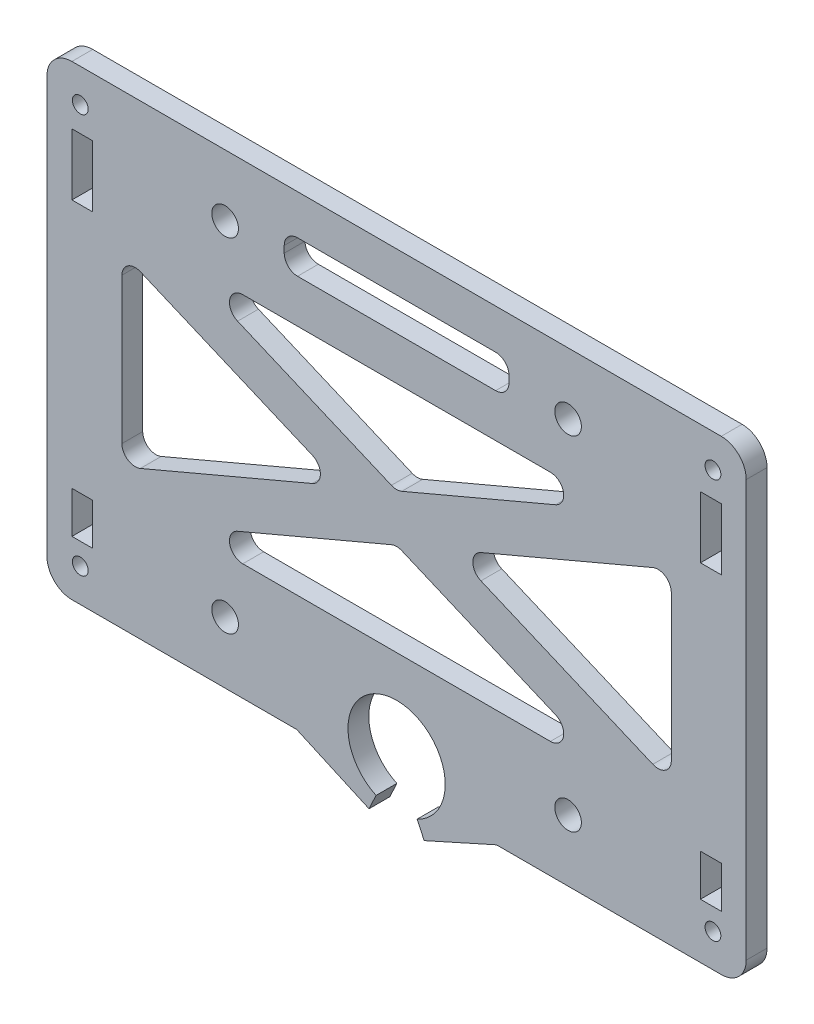
SolidWorks part; units mm, degrees
material "Delrin 2700 NC010, Low Viscosity Acetal Copolymer (SS)"
ref_plane "Front Plane" through (0, 0, 0) normal (0, 0, 1) x (1, 0, 0)
ref_plane "Top Plane" through (0, 0, 0) normal (0, 1, 0) x (1, 0, 0)
ref_plane "Right Plane" through (0, 0, 0) normal (1, 0, 0) x (0, 0, -1)
sketch "Sketch1" plane through (0, 0, 0) normal (0, 0, 1) x (1, 0, 0)
  line L0 (0, -1000) -> (0, 49000) construction
  line L1 (24.765, 17.78) -> (-24.765, 17.78)
  line L2 (26.67, 15.875) -> (26.67, -17.78)
  line L3 (26.67, -17.78) -> (-26.67, -17.78)
  line L4 (-26.67, 15.875) -> (-26.67, -17.78)
  line L5 (26.67, 17.78) -> (-26.67, -17.78) construction
  line L6 (26.67, -17.78) -> (-26.67, 17.78) construction
  line L7 (-1000, 0) -> (49000, 0) construction
  line L8 (-7.62, -17.78) -> (-2.104, -20.26)
  line L15 (-2.104, -20.26) -> (0, -15.748)
  line L16 (7.62, -17.78) -> (2.104, -20.26)
  line L17 (2.104, -20.26) -> (0, -15.748)
  line L18 (0, 0) -> (-24.2469, 20.3456) construction
  circle A0 centre (0, -15.748) radius 3.7084
  circle A1 centre (-24.13, 15.24) radius 0.6032
  circle A2 centre (-13.08, -13.08) radius 1.016
  circle A3 centre (24.13, 15.24) radius 0.6033
  circle A4 centre (-13.08, 13.08) radius 1.016
  circle A5 centre (13.08, 13.08) radius 1.016
  circle A6 centre (13.08, -13.08) radius 1.016
  arc A7 (24.765, -17.78) -> (26.67, -15.875) centre (24.765, -15.875) ccw
  arc A8 (-24.765, -17.78) -> (-26.67, -15.875) centre (-24.765, -15.875) cw
  arc A9 (-24.765, 17.78) -> (-26.67, 15.875) centre (-24.765, 15.875) ccw
  arc A10 (24.765, 17.78) -> (26.67, 15.875) centre (24.765, 15.875) cw
  circle A11 centre (24.13, -15.24) radius 0.6033
  circle A12 centre (-24.13, -15.24) radius 0.6032
  circle A13 centre (0, -15.748) radius 4.9784
  point P0 (0, 0)
  point P9 (0, 0)
  point P11 (0, -7.366)
  point P53 (-13.97, 0)
  dimension "D6" = 7.4168
  dimension "D7" = 1.2065
  dimension "D9" = 2.032
  dimension "D14" = 1.905
  dimension "D15" = 1.905
  dimension "D30" = 2.54
  dimension "D1" = 35.56
  dimension "D4" = 53.34
  dimension "D5" = 15.748
  dimension "D8" = 2.54
  dimension "D10" = 13.08
  dimension "D11" = 13.08
  dimension "D19" = 40
  dimension "D20" = 8.382
  dimension "D21" = 4
  dimension "D23" = 13.97
  dimension "D27" = 7.62
  dimension "D28" = 25
  dimension "D26" = 1.27
extrude "Boss-Extrude1" add sketch "Sketch1" along normal blind 1.5875 contours A10 L1 A9 L4 L3 A0 L2 A6 A5 A4 A1 A2 A3 | L3 A13 L15 A0 | A13 L3 L8 | L3 A13 A0 | L17 A13 L3 A0 | A13 L16 L3 region at (0, 0.4732, 0) region at (5.0756, -18.4873, 0) region at (-5.0756, -18.4873, 0) region at (2.9865, -18.87, 0) region at (3.8235, -17.6582, 0) region at (-2.9865, -18.87, 0)
ref_axis "Axis1" through (0, 0, 0) along (0, 0, 1)
sketch "Sketch2" plane through (0, 0, 1.5875) normal (0, 0, 1) x (1, 0, 0)
  line L0 (0, -1000) -> (0, 49000) construction
  line L1 (-1000, 0) -> (49000, 0) construction
  line L2 (21.0732, -7.1467) -> (-16.7276, 8.89)
  line L3 (20.955, 8.89) -> (-20.955, 8.89)
  line L4 (20.955, 8.89) -> (20.955, -8.89)
  line L5 (20.955, -8.89) -> (-20.955, -8.89)
  line L6 (-20.955, 8.89) -> (-20.955, -8.89)
  line L7 (20.955, 8.89) -> (-20.955, -8.89) construction
  line L8 (20.955, -8.89) -> (-20.955, 8.89) construction
  line L9 (16.7276, 8.89) -> (-20.955, -7.0966)
  line L10 (16.7276, -8.89) -> (-20.955, 7.0966)
  line L11 (20.955, 7.0966) -> (-16.7276, -8.89)
  line L12 (21.5998, 7.3701) -> (-20.3102, -10.4099) construction
  line L13 (20.3102, 10.4099) -> (-21.5998, -7.3701) construction
  line L14 (20.3102, -10.4099) -> (-21.5998, 7.3701) construction
  line L15 (21.5998, -7.3701) -> (-20.3102, 10.4099) construction
  line L16 (24.765, 17.78) -> (-24.765, 17.78) construction
  line L17 (8.5725, 14.732) -> (-8.5725, 14.732)
  line L18 (8.5725, 14.732) -> (8.5725, 12.192)
  line L19 (8.5725, 12.192) -> (-8.5725, 12.192)
  line L20 (-8.5725, 14.732) -> (-8.5725, 12.192)
  line L21 (8.5725, 14.732) -> (-8.5725, 12.192) construction
  line L22 (8.5725, 12.192) -> (-8.5725, 14.732) construction
  point P4 (0, 0)
  point P26 (0, 13.462)
  dimension "D3" = 17.78
  dimension "D4" = 41.91
  dimension "D5" = 3.048
  dimension "D6" = 3.302
  dimension "D7" = 17.145
  dimension "D1" = 1.651
  dimension "D2" = 1.651
extrude "Speed Holes" cut sketch "Sketch2" against normal up to next contours L9 L10 L6 | L9 L3 L2 | L4 L11 L2 | L10 L11 L5 | L17 L20 L19 L18 region at (15.3791, 0, 1.5875) region at (0, 6.5245, 1.5875) region at (0, -6.5245, 1.5875) region at (-15.3791, 0, 1.5875) region at (0, 13.462, 1.5875)
fillet "Fillet1" radius 1.016 16 edges at (-16.7276, -8.89, 0.7937) (-20.955, -7.0966, 0.7937) (0, 1.7934, 0.7937) (16.7276, -8.89, 0.7937) (20.955, -7.0966, 0.7937) (20.955, 7.0966, 0.7937) (-4.2274, 0, 0.7937) (16.7276, 8.89, 0.7937) (4.2274, 0, 0.7937) (-16.7276, 8.89, 0.7937) (0, -1.7934, 0.7937) (-20.955, 7.0966, 0.7937) (-8.5725, 14.732, 0.7937) (-8.5725, 12.192, 0.7937) (8.5725, 14.732, 0.7937) (8.5725, 12.192, 0.7937)
sketch "Sketch5" plane through (0, 0, 1.5875) normal (0, 0, 1) x (1, 0, 0)
  line L0 (24.765, 8.6288) -> (23.1775, 8.6288) construction
  line L1 (24.765, -10.4212) -> (23.1775, -10.4212) construction
  line L2 (24.765, -10.4212) -> (23.1775, -10.4212)
  line L3 (23.1775, -10.4212) -> (23.1775, -13.5962)
  line L4 (24.765, 8.6288) -> (23.1775, 8.6288)
  line L5 (23.1775, -13.5962) -> (24.765, -13.5962)
  line L6 (24.765, -13.5962) -> (24.765, -10.4212)
  line L8 (24.765, 8.6288) -> (24.765, 13.3278)
  line L9 (24.765, 13.3278) -> (23.1775, 13.3278)
  line L10 (23.1775, 13.3278) -> (23.1775, 8.6288)
  dimension "D1" = 4.699
  dimension "D2" = 3.175
extrude "Cut-Extrude1" cut sketch "Sketch5" against normal through all
mirror "Mirror1" about plane through (0, 0, 0) normal (1, 0, 0) of "Cut-Extrude1"
